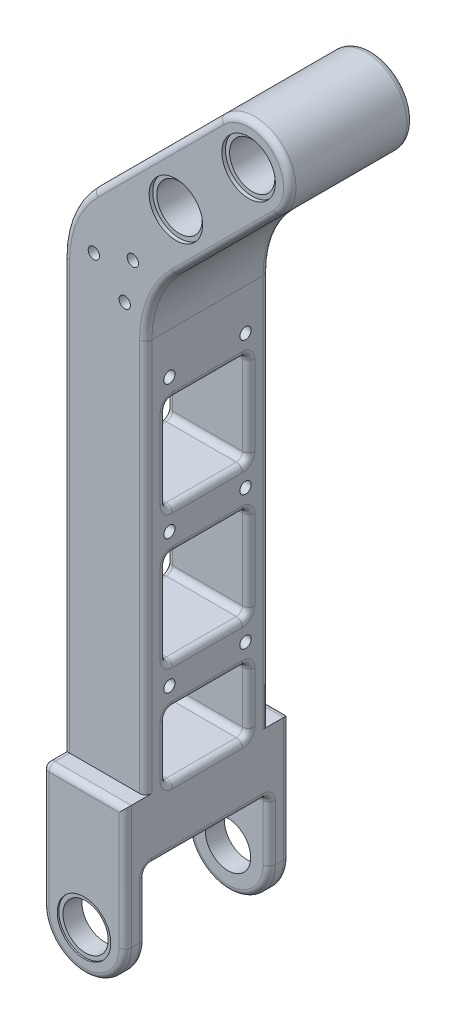
SolidWorks part; units mm, degrees
material "6061 合金"
ref_plane "前视基准面" through (0, 0, 0) normal (0, 0, 1) x (1, 0, 0)
ref_plane "上视基准面" through (0, 0, 0) normal (0, 1, 0) x (1, 0, 0)
ref_plane "右视基准面" through (0, 0, 0) normal (1, 0, 0) x (0, 0, -1)
other "Configuration Table"
sketch "草图1" plane through (0, 0, 0) normal (0, 0, 1) x (1, 0, 0)
  circle A0 centre (0, 0) radius 20
  circle A1 centre (0, 0) radius 11
  dimension "D1" = 40
  dimension "D2" = 22
extrude "凸台-拉伸1" add sketch "草图1" along normal blind 60 contours A1 | A0 region at (0, 0, 0)
ref_plane "基准面1" through (0, 0, 30) normal (0, 0, 1) x (1, 0, 0)
sketch "草图2" plane through (0, 0, 30) normal (0, 0, 1) x (1, 0, 0)
  line L0 (0, 0) -> (-70, -70) construction
  line L1 (-70, -70) -> (-70, -320) construction
  line L2 (0, -57.3148) -> (0, 49.9409) construction
  line L3 (-56.8582, 0) -> (46.4003, 0) construction
  line L4 (-14.1421, 14.1421) -> (-90, -61.7157)
  line L5 (14.1421, -14.1421) -> (-50, -78.2843)
  line L6 (-90, -61.7157) -> (-90, -320)
  line L7 (-50, -78.2843) -> (-50, -320)
  line L8 (-90, -320) -> (-50, -320)
  circle A2 centre (0, 0) radius 20 construction
  arc A3 (-14.1421, 14.1421) -> (14.1421, -14.1421) centre (0, 0) ccw
  dimension "D1" = 45
  dimension "D2" = 250
  dimension "D3" = 70
  dimension "D4" = 40
  dimension "D5" = 40
extrude "凸台-拉伸2" add sketch "草图2" along normal mid plane 60 contours L7 L8 L6 L4 A3 L5
sketch "草图4" plane through (0, 0, 60) normal (0, 0, 1) x (1, 0, 0)
  line L0 (-90, -61.7157) -> (-90, -320) construction
  line L1 (-90, -290) -> (-50, -290)
  line L2 (-90, -290) -> (-90, -350)
  line L4 (-50, -290) -> (-50, -350)
  line L5 (-50, -78.2843) -> (-50, -320) construction
  line L6 (-90, -320) -> (-50, -320) construction
  arc A0 (-90, -350) -> (-50, -350) centre (-70, -350) ccw
  circle A1 centre (-70, -350) radius 11
  dimension "D3" = 22
  dimension "D1" = 30
  dimension "D2" = 30
extrude "凸台-拉伸3" add sketch "草图4" along normal blind 10
mirror "镜向1" about plane through (0, 0, 30) normal (0, 0, 1) of "凸台-拉伸3"
sketch "草图5" plane through (0, 0, 0) normal (0, 1, 0) x (1, 0, 0)
  line L0 (0, 0) -> (0, -78.0582) construction
ref_plane "基准面2" through (-70, 0, 0) normal (-1, 0, 0) x (0, 0, 1)
sketch "草图7" plane through (-70, 0, 0) normal (-1, 0, 0) x (0, 0, 1)
  line L0 (-34.1239, -350) -> (109.535, -350) construction
sketch "草图8" plane through (0, 0, 60) normal (0, 0, 1) x (1, 0, 0)
  line L0 (0, 0) -> (-70, -70) construction
  circle A0 centre (-35.3553, -35.3553) radius 11
  dimension "D1" = 22
  dimension "D2" = 50
extrude "切除-拉伸1" cut sketch "草图8" against normal blind 100
fillet "圆角1" radius 50 2 edges at (-90, -61.7157, 30) (-50, -78.2843, 30)
fillet "圆角2" radius 3 34 edges at (-50, -320, 70) (-70, -370, 70) (-50, -335, 60) (-70, -370, 60) (-50, -335, 0) (-70, -370, 0) (-50, -320, -10) (-70, -370, -10) (-70, -320, 60) (-50, -320, 30) (-70, -320, 0) (-90, -290, 65) (-90, -320, 70) (-90, -335, 60) (-90, -320, 30) (-90, -335, 0) (-90, -320, -10) (-90, -290, -5) (-50, -194.4975, 0) (-46.194, -79.8608, 0) (-10.6066, -38.8909, 0) (14.1421, 14.1421, 0) (-44.7487, -16.4645, 0) (-86.194, -63.2922, 0) (-90, -186.2132, 0) (14.1421, 14.1421, 60) (-10.6066, -38.8909, 60) (-46.194, -79.8608, 60) (-50, -194.4975, 60) (-90, -186.2132, 60) (-86.194, -63.2922, 60) (-44.7487, -16.4645, 60) (-70, -290, 70) (-70, -290, -10)
sketch "草图9" plane through (0, 0, 70) normal (0, 0, 1) x (1, 0, 0)
  circle A0 centre (-70, -350) radius 13
  dimension "D1" = 26
extrude "切除-拉伸2" cut sketch "草图9" against normal blind 0.75
sketch "草图10" plane through (0, 0, -10) normal (0, 0, -1) x (-1, 0, 0)
  circle A0 centre (70, -350) radius 13
  dimension "D1" = 26
extrude "切除-拉伸3" cut sketch "草图10" against normal blind 0.75 contours A0
sketch "草图11" plane through (-90, 0, 0) normal (-1, 0, 0) x (0, 0, 1)
  circle A0 centre (48.5, -118.9949) radius 2.75
  circle A1 centre (48.5, -183.9949) radius 2.75
  circle A2 centre (48.5, -248.9949) radius 2.75
  circle A3 centre (11.5, -248.9949) radius 2.75
  circle A4 centre (11.5, -183.9949) radius 2.75
  circle A5 centre (11.5, -118.9949) radius 2.75
  dimension "D1" = 5.5
extrude "切除-拉伸4" cut sketch "草图11" against normal through all contours A1 | A2 | A0 | A3 | A4 | A5 region at (-90, -183.9949, 48.5) region at (-90, -248.9949, 48.5)
sketch "草图12" plane through (-90, 0, 0) normal (-1, 0, 0) x (0, 0, 1)
  line L0 (30, -62.0134) -> (30, -339.6946) construction
  line L1 (10, -128.9949) -> (50, -128.9949)
  line L2 (10, -128.9949) -> (10, -173.9949)
  line L3 (10, -173.9949) -> (50, -173.9949)
  line L4 (50, -128.9949) -> (50, -173.9949)
  line L5 (10, -193.9949) -> (50, -193.9949)
  line L6 (10, -193.9949) -> (10, -238.9949)
  line L7 (10, -238.9949) -> (50, -238.9949)
  line L8 (50, -193.9949) -> (50, -238.9949)
  line L9 (10, -258.9949) -> (50, -258.9949)
  line L10 (10, -258.9949) -> (10, -290)
  line L11 (10, -290) -> (50, -290)
  line L12 (50, -258.9949) -> (50, -290)
  line L13 (19.5, -173.9949) -> (40.5, -173.9949)
  line L14 (19.5, -173.9949) -> (19.5, -193.9949)
  line L15 (19.5, -193.9949) -> (40.5, -193.9949)
  line L16 (40.5, -173.9949) -> (40.5, -193.9949)
  line L17 (19.5, -238.9949) -> (40.5, -238.9949)
  line L18 (19.5, -238.9949) -> (19.5, -258.9949)
  line L19 (19.5, -258.9949) -> (40.5, -258.9949)
  line L20 (40.5, -238.9949) -> (40.5, -258.9949)
  line L21 (60, -82.4264) -> (60, -290) construction
  line L22 (0, -290) -> (0, -82.4264) construction
  line L23 (57, -320) -> (3, -320) construction
  circle A0 centre (48.5, -118.9949) radius 2.75 construction
  circle A1 centre (48.5, -183.9949) radius 2.75 construction
  circle A2 centre (48.5, -248.9949) radius 2.75 construction
  dimension "D1" = 10
  dimension "D2" = 10
  dimension "D3" = 10
  dimension "D4" = 8
  dimension "D5" = 10
  dimension "D6" = 10
  dimension "D7" = 10
  dimension "D8" = 30
extrude "减重" cut sketch "草图12" against normal through all contours L0 L1 L2 L3 | L15 L0 L17 L7 L8 L5 | L0 L5 L6 L7 | L19 L0 L11 L12 L9 | L0 L9 L10 L11 | L1 L0 L13 L3 L4 region at (-90, -151.4949, 40) region at (-90, -151.4949, 20) region at (-90, -216.4949, 40) region at (-90, -216.4949, 20) region at (-90, -274.4975, 40) region at (-90, -274.4975, 20)
fillet "圆角3" radius 3 36 edges at (-90, -258.9949, 30) (-50, -258.9949, 30) (-50, -290, 30) (-90, -290, 30) (-50, -238.9949, 30) (-50, -193.9949, 30) (-90, -193.9949, 30) (-90, -238.9949, 30) (-50, -173.9949, 30) (-90, -173.9949, 30) (-50, -128.9949, 30) (-90, -128.9949, 30) (-70, -290, 10) (-90, -274.4975, 10) (-70, -258.9949, 10) (-50, -274.4975, 10) (-50, -274.4975, 50) (-70, -258.9949, 50) (-90, -274.4975, 50) (-70, -290, 50) (-50, -216.4949, 50) (-70, -193.9949, 50) (-90, -216.4949, 50) (-70, -238.9949, 50) (-70, -238.9949, 10) (-90, -216.4949, 10) (-70, -193.9949, 10) (-50, -216.4949, 10) (-70, -173.9949, 10) (-90, -151.4949, 10) (-70, -128.9949, 10) (-50, -151.4949, 10) (-50, -151.4949, 50) (-70, -128.9949, 50) (-90, -151.4949, 50) (-70, -173.9949, 50)
sketch "草图13" plane through (0, 0, 60) normal (0, 0, 1) x (1, 0, 0)
  circle A0 centre (0, 0) radius 13
  circle A1 centre (-35.3553, -35.3553) radius 13
  dimension "D1" = 26
  dimension "D2" = 26
extrude "切除-拉伸6" cut sketch "草图13" against normal blind 1.75
sketch "草图14" plane through (0, 0, 0) normal (0, 0, -1) x (-1, 0, 0)
  circle A0 centre (0, 0) radius 13
  circle A1 centre (35.3553, -35.3553) radius 13
  dimension "D1" = 26
  dimension "D2" = 26
extrude "切除-拉伸7" cut sketch "草图14" against normal blind 1.75
sketch "草图15" plane through (0, 0, 0) normal (0, 0, -1) x (-1, 0, 0)
  line L0 (0, 0) -> (70, -350) construction
  line L1 (56.2719, -67.2005) -> (60.1942, -86.8121) construction
  line L2 (70, -350) -> (204.3541, -323.1292) construction
  circle A0 centre (56.2719, -67.2005) radius 2.75
  circle A1 centre (75.2172, -73.6095) radius 2.75
  circle A2 centre (60.1942, -86.8121) radius 2.75
  dimension "D1" = 5.5
  dimension "D2" = 20
  dimension "D3" = 20
  dimension "D4" = 20
  dimension "D5" = 42
  dimension "D6" = 270
extrude "切除-拉伸8" cut sketch "草图15" against normal through all contours A2 | A0 | A1 region at (-56.2719, -67.2005, 0) region at (-60.1942, -86.8121, 0)
ref_plane "基准面3" through (0, 0, 0) normal (0.9806, -0.1961, 0) x (0, 0, -1)
